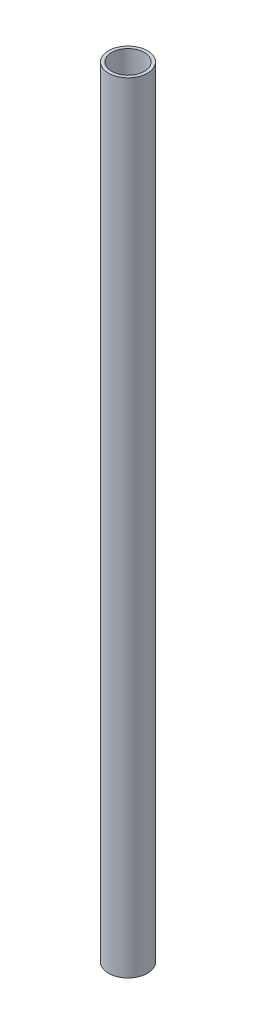
SolidWorks part; units mm, degrees
ref_plane "Front Plane" through (0, 0, 0) normal (0, 0, 1) x (1, 0, 0)
ref_plane "Top Plane" through (0, 0, 0) normal (0, 1, 0) x (1, 0, 0)
ref_plane "Right Plane" through (0, 0, 0) normal (1, 0, 0) x (0, 0, -1)
sketch "Sketch1" plane through (0, 0, 0) normal (0, 1, 0) x (1, 0, 0)
  circle A0 centre (0, 0) radius 12.5
  circle A1 centre (0, 0) radius 10.5
  dimension "D1" = 25
  dimension "D2" = 21
extrude "Boss-Extrude1" add sketch "Sketch1" along normal blind 500
equation "\"D1@Sketch1\" = \"cf_tube_outer_diameter\""
equation "\"D1@Boss-Extrude1\"= \"mid_tube_length\""
equation "\"cf_tube_outer_diameter\" = 25mm"
equation "\"mid_plate_mid_to_top\" = 100mm"
equation "\"mid_plate_mid_to_bottom\" = 100mm"
equation "\"mid_plate_horizontal_spacing\" = 250mm"
equation "\"mid_tube_length\" = 500mm"
equation "\"cf_tube_inner_diameter\" = 21mm"
equation "\"D2@Sketch1\"=\"cf_tube_inner_diameter\""
